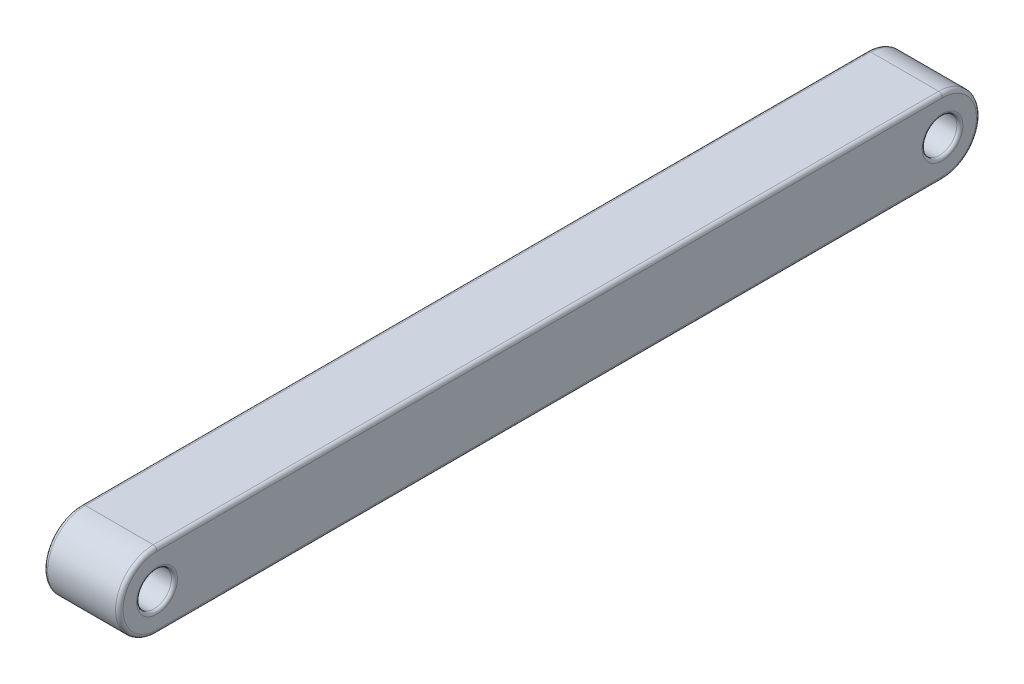
SolidWorks part; units mm, degrees
ref_plane "Front Plane" through (0, 0, 0) normal (0, 0, 1) x (1, 0, 0)
ref_plane "Top Plane" through (0, 0, 0) normal (0, 1, 0) x (1, 0, 0)
ref_plane "Right Plane" through (0, 0, 0) normal (1, 0, 0) x (0, 0, -1)
sketch "Sketch1" plane through (0, 0, 0) normal (1, 0, 0) x (0, 0, -1)
  line L1 (0, 0) -> (24, 0)
  line L2 (0, 0) -> (0, -2.5) construction
  line L3 (0, -2.5) -> (24, -2.5)
  line L4 (24, 0) -> (24, -2.5) construction
  line L5 (0, 0) -> (-1, 0)
  line L6 (0, 0) -> (0, -2.5) construction
  line L7 (0, -2.5) -> (-1, -2.5)
  line L8 (-1, 0) -> (-1, -2.5) construction
  line L9 (24, 0) -> (25, 0)
  line L10 (24, 0) -> (24, -2.5) construction
  line L11 (24, -2.5) -> (25, -2.5)
  line L12 (25, 0) -> (25, -2.5) construction
  line L16 (0, -1.25) -> (-1, -1.25) construction
  line L17 (24, -1.25) -> (25, -1.25) construction
  circle A0 centre (-1, -1.25) radius 0.575
  arc A1 (-1, -2.5) -> (-1, 0) centre (-1, -1.25) cw
  circle A2 centre (25, -1.25) radius 0.575
  arc A3 (25, 0) -> (25, -2.5) centre (25, -1.25) cw
  dimension "D1" = 1.15
  dimension "D4" = 1.15
  dimension "D2" = 2.5
  dimension "D3" = 2.5
  dimension "D5" = 26
  dimension "D6" = 2.5
  dimension "D7" = 1
  dimension "D8" = 1
extrude "Boss-Extrude1" add sketch "Sketch1" along normal blind 2.5 contours A3 L9 L1 L5 A1 L7 L3 L11 A2 A0 region at (0, -1.25, -12)
fillet "Fillet1" radius 0.125 8 edges at (2.5, -1.25, -26.25) (2.5, 0, -12) (2.5, -1.25, 2.25) (0, -1.25, -26.25) (0, 0, -12) (0, -1.25, 2.25) (2.5, -2.5, -12) (0, -2.5, -12)
fillet "Fillet2" radius 0.1 4 edges at (0, -1.25, -25.575) (2.5, -1.25, -25.575) (0, -1.25, 0.425) (2.5, -1.25, 0.425)
